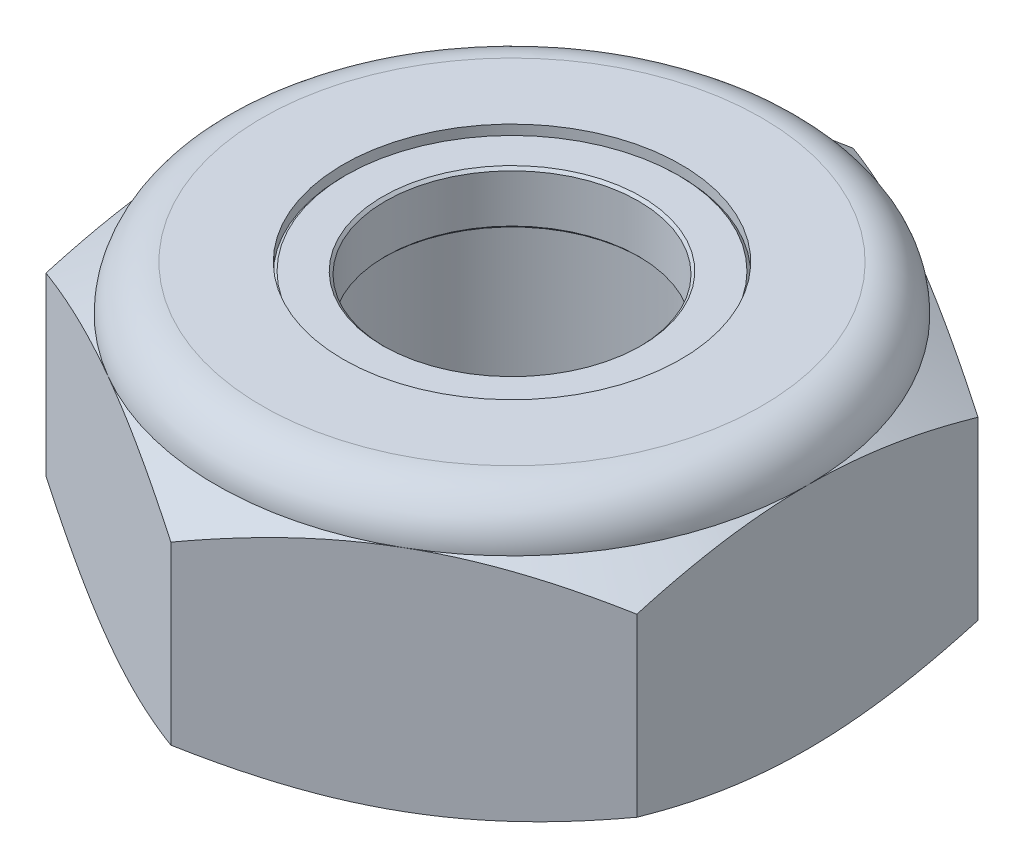
SolidWorks part; units mm, degrees
material "Alloy Steel"
ref_plane "Front" through (0, 0, 0) normal (0, 0, 1) x (1, 0, 0)
ref_plane "Top" through (0, 0, 0) normal (0, 1, 0) x (1, 0, 0)
ref_plane "Right" through (0, 0, 0) normal (1, 0, 0) x (0, 0, -1)
sketch "Sketch1" plane through (0, 0, 0) normal (0, 1, 0) x (1, 0, 0)
  line L1 (0, 6.4158) -> (-5.5563, 3.2079)
  line L2 (-5.5563, 3.2079) -> (-5.5563, -3.2079)
  line L3 (-5.5563, -3.2079) -> (0, -6.4158)
  line L4 (0, -6.4158) -> (5.5562, -3.2079)
  line L5 (5.5562, -3.2079) -> (5.5562, 3.2079)
  line L6 (5.5562, 3.2079) -> (0, 6.4158)
  circle A0 centre (0, 0) radius 5.5563 construction
  circle A1 centre (0, 0) radius 3.175
  dimension "Thread Dia" = 6.35
  dimension "Hex Flats" = 11.1125
extrude "Extrude1" add sketch "Sketch1" along normal blind 5.1594
sketch "Sketch2" plane through (0, 0, 0) normal (1, 0, 0) x (0, 0, -1)
  line L0 (6.4158, 5.1594) -> (6.4158, 0) construction
  line L1 (6.4158, 5.1594) -> (6.4158, 3.8032)
  line L2 (6.4158, 0.4963) -> (5.5563, 0)
  line L3 (5.5563, 0) -> (6.4158, 0)
  line L4 (5.5563, 0) -> (-5.5563, 0) construction
  line L5 (6.4158, 3.8032) -> (5.5563, 4.2995)
  line L6 (3.2079, 5.1594) -> (6.4158, 5.1594) construction
  line L7 (5.5563, 0) -> (5.5563, 4.2995) construction
  line L8 (4.6964, 5.1594) -> (6.4158, 5.1594)
  line L9 (6.4158, 0.4963) -> (6.4158, 0)
  line L10 (0, 0) -> (0, 5.1594) construction
  line L11 (-3.2079, 5.1594) -> (3.2079, 5.1594) construction
  arc A0 (5.5563, 4.2995) -> (4.6964, 5.1594) centre (4.6964, 4.2995) ccw
  dimension "D1" = 30
  dimension "D2" = 30
  dimension "D3" = 0.8599
revolve "Cut-Revolve1" cut sketch "Sketch2" angle 360 about L10
sketch "Sketch4" plane through (0, 0, 0) normal (0, -1, 0) x (1, 0, 0)
  circle A0 centre (0, 0) radius 3.175 construction
  circle A2 centre (0, 0) radius 3.175
curve "Helix/Spiral1" pitch 1.27 height 6.4294 turns 5.0625 parameters "Pitch"=1.27
sketch "Sketch3" plane through (0, 5.1594, 0) normal (0, 1, 0) x (1, 0, 0)
  circle A0 centre (0, 0) radius 3.175 construction
  circle A1 centre (0, 0) radius 3.175
extrude "Extrude-Thin1" add sketch "Sketch3" against normal blind 1 from offset 0.15 separate body thin offset against normal yes thin type one direction reverse wall 0.7937
chamfer "Chamfer1" distance 0.05 angle 45 4 edges at (0, 5.0094, 3.175) (2.3812, 5.0094, 0) (0, 4.0094, 3.175) (2.3812, 4.0094, 0)
sketch "Sketch8" plane through (0, 5.1594, 0) normal (0, 1, 0) x (1, 0, 0)
  line L0 (0, 6.4158) -> (0, -6.4158) construction
  line L1 (0, -6.4158) -> (2.7781, -4.8119) construction
  line L2 (0, 0) -> (2.2451, -2.2451) construction
  circle A0 centre (0, 0) radius 3.175 construction
  dimension "D1" = 45
sketch "Sketch5" [suppressed] plane through (0, 0, 0) normal (1, 0, 0) x (0, 0, -1)
  line L0 (3.175, -1.1113) -> (3.175, 0)
  line L1 (3.175, -1.1113) -> (2.3501, -0.635)
  line L2 (2.3501, -0.635) -> (2.3501, -0.4763)
  line L3 (2.3501, -0.4763) -> (3.175, 0)
  line L5 (3.175, -0.5556) -> (2.3501, -0.5556) construction
  line L6 (2.7626, -0.8731) -> (2.7626, -0.2381) construction
  dimension "D1" = 0.1588
  dimension "D2" = 0.635
  dimension "D3" = 60
  dimension "D4" = 0.8249
sweep "Sweep1" [suppressed] add profiles "Sketch5" path "Helix/Spiral1"
sketch "Sketch6" [suppressed] plane through (0, 0, 0) normal (0, -1, 0) x (1, 0, 0)
  circle A1 centre (0, 0) radius 3.175
  circle A2 centre (0, 0) radius 3.175
  dimension "D1" = 0
extrude "Cut-Extrude1" [suppressed] cut sketch "Sketch6" against normal through all draft 45 and the other way through all
sketch "Sketch7" [suppressed] plane through (0, 5.1594, 0) normal (0, 1, 0) x (1, 0, 0)
  circle A1 centre (0, 0) radius 3.175
  circle A2 centre (0, 0) radius 3.175
  dimension "D1" = 0
extrude "Cut-Extrude2" [suppressed] cut sketch "Sketch7" along normal through all and the other way through all draft 45 from offset 1 offset against normal yes
combine bodies "Combine1" [suppressed] operation type add bodies to combine 138 135
ref_plane "Contact Plane 1" through (0, 0, 0) normal (0, -1, 0) x (-1, 0, 0)
ref_plane "Contact Plane 2" through (0, 5.1594, 0) normal (0, 1, 0) x (1, 0, 0)
ref_axis "Center Axis 1" [suppressed] through (0, 5.9668, 0) along (0, -1, 0)
equation "\"D3@Helix/Spiral1\"=\"Pitch@Helix/Spiral1\"+\"Height@Extrude1\""
equation "\"D1@Sketch5\"=\"Pitch@Helix/Spiral1\"*.125"
equation "\"D2@Sketch5\"=\"Pitch@Helix/Spiral1\"*.50"
equation "\"D3@Sketch2\"=\"Height@Extrude1\"/6"
equation "\"D5@Extrude-Thin1\"=\"Pitch@Helix/Spiral1\"*.625"
